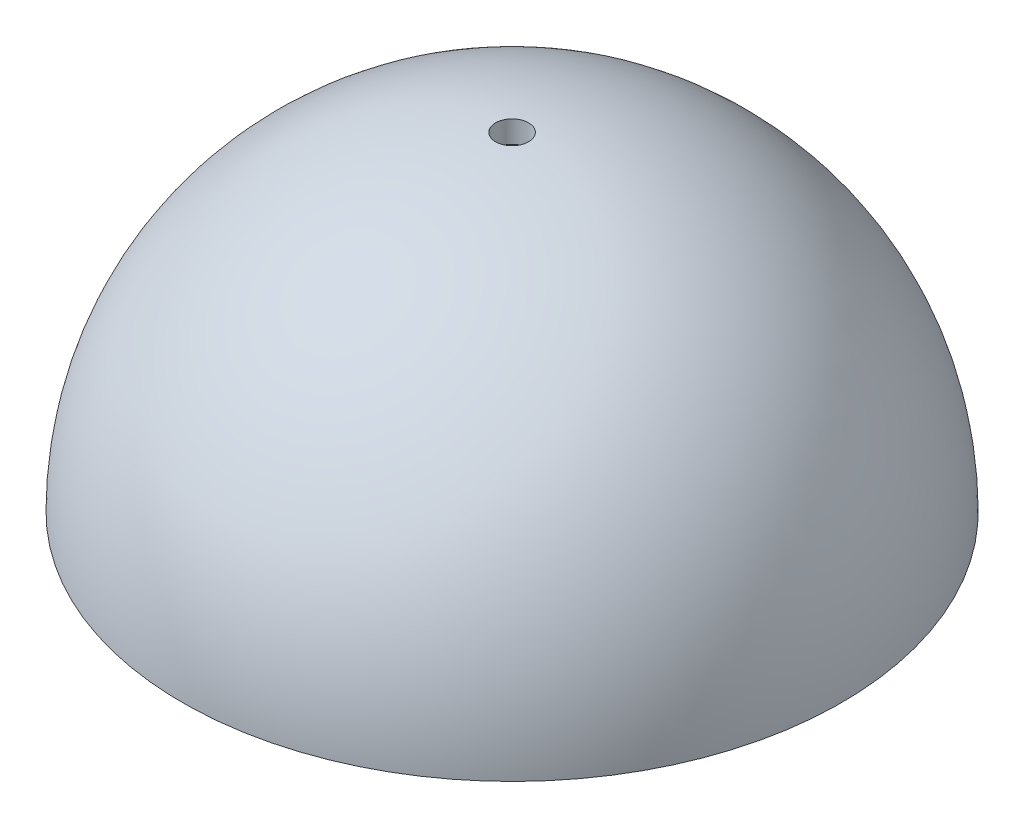
SolidWorks part; units mm, degrees
ref_plane "Front Plane" through (0, 0, 0) normal (0, 0, 1) x (1, 0, 0)
ref_plane "Top Plane" through (0, 0, 0) normal (0, 1, 0) x (1, 0, 0)
ref_plane "Right Plane" through (0, 0, 0) normal (1, 0, 0) x (0, 0, -1)
sketch "Sketch1" plane through (0, 0, 0) normal (0, 0, 1) x (1, 0, 0)
  line L0 (0, 0) -> (0, 150)
  line L1 (0, 0) -> (-150, 0)
  arc A0 (-150, 0) -> (0, 150) centre (0, 0) cw
  dimension "D1" = 150
revolve "Revolve1" add sketch "Sketch1" angle 360 about L0
shell "Shell1" thickness 10 removed face at (0, 0, -150)
sketch "Sketch2" plane through (0, 0, 0) normal (0, 1, 0) x (1, 0, 0)
  circle A0 centre (0, 0) radius 7.5
  dimension "D1" = 15
extrude "Cut-Extrude3" cut sketch "Sketch2" against normal through all and the other way through all
